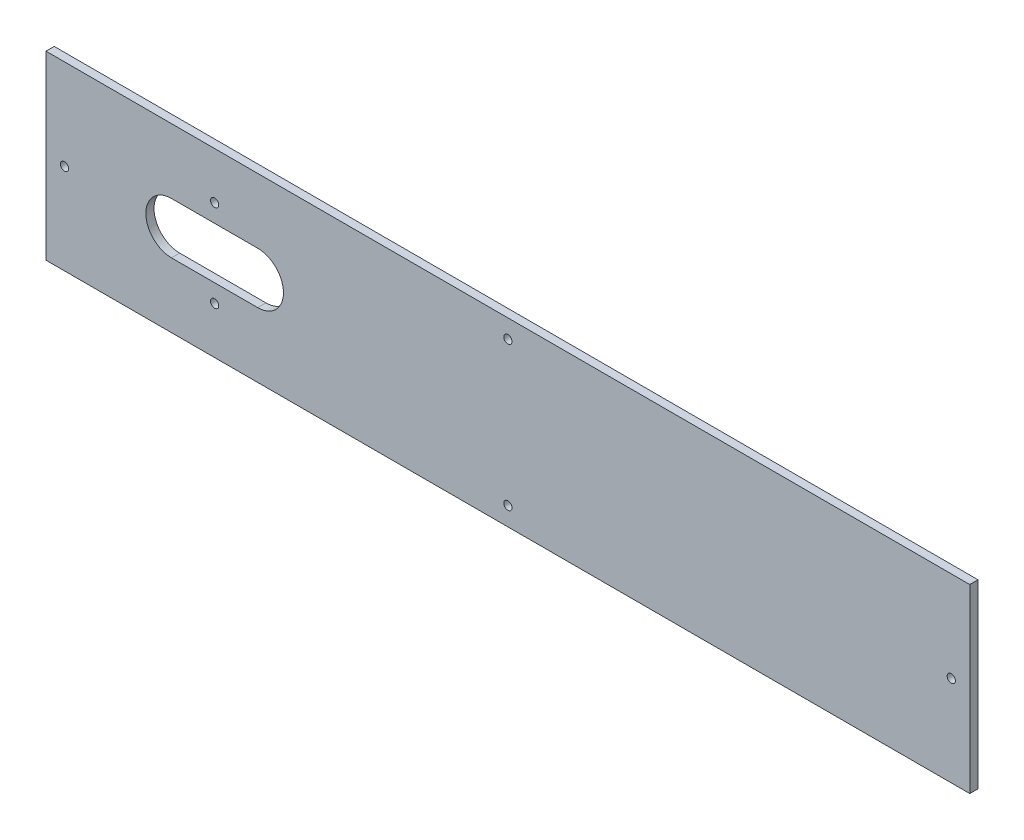
SolidWorks part; units mm, degrees
ref_plane "Piano frontale" through (0, 0, 0) normal (0, 0, 1) x (1, 0, 0)
ref_plane "Piano superiore" through (0, 0, 0) normal (0, 1, 0) x (1, 0, 0)
ref_plane "Piano destro" through (0, 0, 0) normal (1, 0, 0) x (0, 0, -1)
sketch "Schizzo1" plane through (0, 0, 0) normal (0, 0, 1) x (1, 0, 0)
  line L0 (-224.5, 351.6275) -> (-224.5, -66.2585) construction
  line L1 (0, 0) -> (-449, 0)
  line L2 (0, 0) -> (0, 88)
  line L3 (0, 88) -> (-449, 88)
  line L4 (-449, 0) -> (-449, 88)
  line L5 (-387.9788, 44) -> (120.8821, 44) construction
  line L6 (-387.9788, 44) -> (-346.0895, 44) construction
  line L7 (-387.9788, 56.5) -> (-346.0895, 56.5)
  line L8 (-387.9788, 31.5) -> (-346.0895, 31.5)
  arc A0 (-387.9788, 56.5) -> (-387.9788, 31.5) centre (-387.9788, 44) ccw
  circle A1 centre (-9, 44) radius 2
  circle A2 centre (-224.5, 79) radius 2
  circle A3 centre (-440, 44) radius 2
  circle A4 centre (-224.5, 9) radius 2
  arc A5 (-346.0895, 31.5) -> (-346.0895, 56.5) centre (-346.0895, 44) ccw
  circle A6 centre (-367.0341, 65.21) radius 2
  circle A7 centre (-367.0341, 22.79) radius 2
  point P9 (-224.5, 44)
  point P10 (-367.0341, 44)
  dimension "D3" = 4
  dimension "D2" = 4
  dimension "D5" = 4
  dimension "D1" = 449
  dimension "314" = 88
  dimension "D4" = 9
  dimension "D6" = 9
  dimension "D7" = 25
extrude "Estrusione-Estrusione1" add sketch "Schizzo1" along normal blind 4
